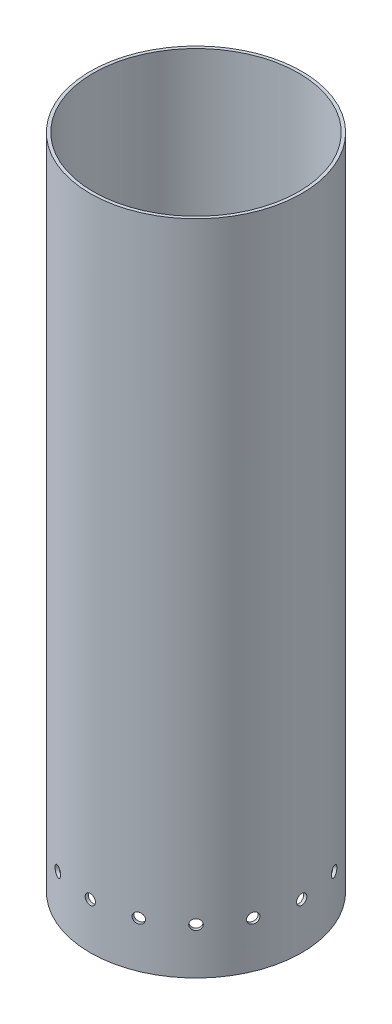
SolidWorks part; units mm, degrees
ref_plane "Front Plane" through (0, 0, 0) normal (0, 0, 1) x (1, 0, 0)
ref_plane "Top Plane" through (0, 0, 0) normal (0, 1, 0) x (1, 0, 0)
ref_plane "Right Plane" through (0, 0, 0) normal (1, 0, 0) x (0, 0, -1)
sketch "Sketch1" plane through (0, 0, 0) normal (0, 1, 0) x (1, 0, 0)
  circle A0 centre (0, 0) radius 63.5
  circle A1 centre (0, 0) radius 65.405
  dimension "D1" = 127
  dimension "D2" = 130.81
extrude "Boss-Extrude1" add sketch "Sketch1" against normal blind 406.4
ref_plane "Plane1" through (0, 0, 65.405) normal (0, 0, 1) x (1, 0, 0)
ref_axis "Axis1" through (0, -406.4, 0) along (0, 1, 0)
sketch "Sketch4" plane through (0, 0, 65.405) normal (0, 0, 1) x (1, 0, 0)
  line L2 (-65.405, -406.4) -> (65.405, -406.4) construction
  circle A0 centre (0, -377.825) radius 3.175
  point P0 (0, -377.825)
  dimension "D2" = 6.35
  dimension "D1" = 28.575
extrude "Cut-Extrude3" cut sketch "Sketch4" against normal up to next
pattern_circular "CirPattern2" count 16 over 360 about axis through (0, -406.4, 0) along (0, 1, 0) of "Cut-Extrude3"
